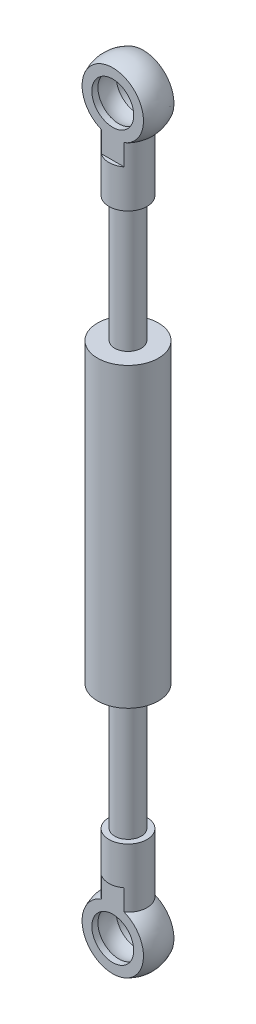
SolidWorks part; units mm, degrees
ref_plane "前基準面" through (0, 0, 0) normal (0, 0, 1) x (1, 0, 0)
ref_plane "上基準面" through (0, 0, 0) normal (0, 1, 0) x (1, 0, 0)
ref_plane "右基準面" through (0, 0, 0) normal (1, 0, 0) x (0, 0, -1)
sketch "草圖1" plane through (0, 0, 0) normal (0, 0, 1) x (1, 0, 0)
  line L0 (2.5, 43) -> (2.5, 43.7583)
  line L1 (-4, 19.5) -> (4, 19.5)
  line L2 (-4, 19.5) -> (-4, -19.5)
  line L3 (-4, -19.5) -> (4, -19.5)
  line L4 (4, 19.5) -> (4, -19.5)
  line L5 (-4, 19.5) -> (4, -19.5) construction
  line L6 (-4, -19.5) -> (4, 19.5) construction
  line L7 (-1.75, 36) -> (1.75, 36)
  line L8 (-1.75, 36) -> (-1.75, -36)
  line L9 (-1.75, -36) -> (1.75, -36)
  line L10 (1.75, 36) -> (1.75, -36)
  line L11 (-1.75, 36) -> (1.75, -36) construction
  line L12 (-1.75, -36) -> (1.75, 36) construction
  line L13 (-2.5, 43) -> (2.5, 43)
  line L14 (-2.5, 43) -> (-2.5, 36)
  line L15 (-2.5, 36) -> (2.5, 36)
  line L16 (2.5, 43) -> (2.5, 36)
  line L17 (-2.5, 43) -> (-2.5, 43.7583)
  line L18 (55, 0) -> (-55, 0) construction
  line L19 (-2.5, -43) -> (-2.5, -43.7583)
  line L20 (2.5, -43) -> (2.5, -36)
  line L21 (-2.5, -36) -> (2.5, -36)
  line L22 (-2.5, -43) -> (-2.5, -36)
  line L23 (-2.5, -43) -> (2.5, -43)
  line L24 (-1.75, -36) -> (1.75, -36)
  line L25 (2.5, -43) -> (2.5, -43.7583)
  line L26 (0, -1000) -> (0, 49000)
  circle A0 centre (0, 47.5) radius 4.5
  circle A1 centre (0, -47.5) radius 4.5
  point P0 (0, 0)
  point P6 (0, 0)
  point P15 (0, 36)
  point P16 (0, 36)
  dimension "D7" = 9
  dimension "D1" = 8
  dimension "D2" = 39
  dimension "D3" = 3.5
  dimension "D4" = 72
  dimension "D5" = 7
  dimension "D6" = 5
revolve "旋轉1" add sketch "草圖1" angle 360 about L26 region at (1.886, 43.2238, 0) region at (1.25, 39.5, 0) region at (1.9099, 47.5, 0) region at (0.875, 27.75, 0) region at (0.875, 0, 0) region at (2.875, 0, 0) region at (0.875, -27.75, 0) region at (1.25, -39.5, 0) region at (1.9099, -47.5, 0) region at (1.886, -43.2238, 0)
sketch "草圖2" plane through (0, 0, 0) normal (0, 0, 1) x (1, 0, 0)
  line L0 (0, -1000) -> (0, 49000)
  circle A0 centre (0, 47.5) radius 3
  circle A1 centre (0, -47.5) radius 3
  point P4 (0, 47.5)
  point P5 (0, -47.5)
  dimension "D1" = 6
  dimension "D2" = 6
revolve "除料-旋轉1" cut sketch "草圖2" angle 360 about L0 region at (1.2732, 47.5, 0) region at (1.2732, -47.5, 0)
sketch "草圖3" plane through (0, 0, 0) normal (1, 0, 0) x (0, 0, -1)
  line L0 (-1.75, 36) -> (1.75, 36) construction
  line L1 (-2, 56) -> (-5, 56)
  line L2 (-2, 56) -> (-2, 41)
  line L3 (-2, 41) -> (-5, 41)
  line L4 (-5, 56) -> (-5, 41)
  line L9 (0, 4.95) -> (0, -4.95) construction
  line L10 (5, 56) -> (5, 41)
  line L11 (2, 41) -> (5, 41)
  line L12 (2, 56) -> (2, 41)
  line L13 (2, 56) -> (5, 56)
  line L14 (4.95, 0) -> (-4.95, 0) construction
  line L15 (2, -56) -> (5, -56)
  line L16 (2, -56) -> (2, -41)
  line L17 (2, -41) -> (5, -41)
  line L18 (5, -56) -> (5, -41)
  line L19 (-5, -56) -> (-5, -41)
  line L20 (-2, -41) -> (-5, -41)
  line L21 (-2, -56) -> (-2, -41)
  line L22 (-2, -56) -> (-5, -56)
  dimension "D1" = 5
  dimension "D2" = 2
  dimension "D3" = 3
  dimension "D4" = 15
extrude "除料-伸長1" cut sketch "草圖3" against normal through all both and the other way through all
sketch "草圖4" plane through (0, 0, 2) normal (0, 0, 1) x (1, 0, 0)
  circle A0 centre (0, 47.5) radius 2.75
  circle A1 centre (0, -47.5) radius 2.75
  point P4 (0, 47.5)
  point P5 (0, -47.5)
  dimension "D1" = 5.5
  dimension "D2" = 5.5
extrude "除料-伸長2" cut sketch "草圖4" against normal through all both and the other way through all
